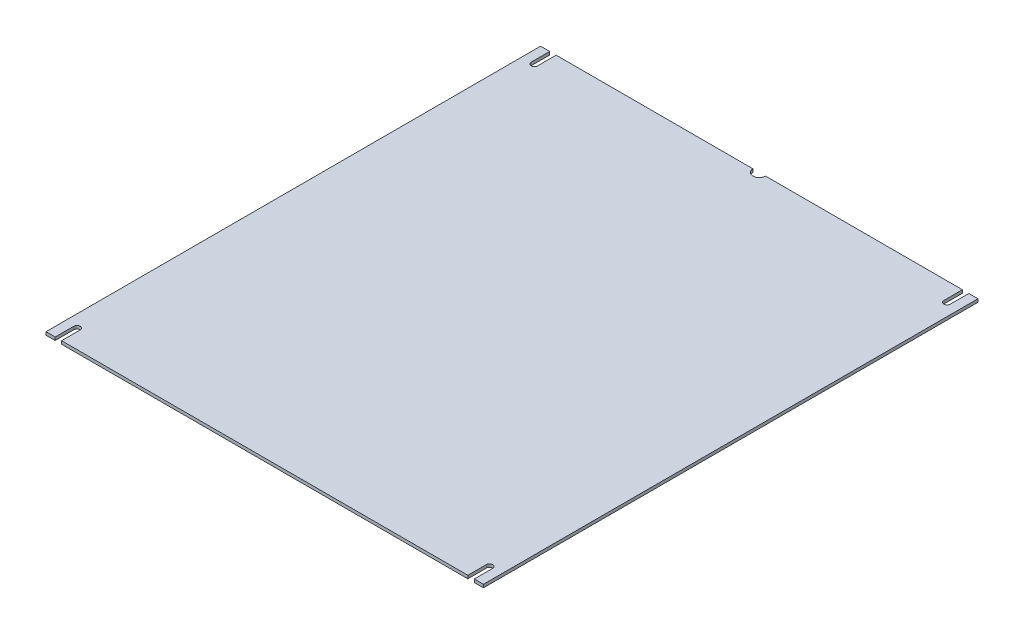
SolidWorks part; units mm, degrees
ref_plane "Front Plane" through (0, 0, 0) normal (0, 0, 1) x (1, 0, 0)
ref_plane "Top Plane" through (0, 0, 0) normal (0, 1, 0) x (1, 0, 0)
ref_plane "Right Plane" through (0, 0, 0) normal (1, 0, 0) x (0, 0, -1)
sketch "Sketch1" plane through (0, 0, 0) normal (0, 1, 0) x (1, 0, 0)
  line L1 (0, 0) -> (449.326, 0)
  line L2 (0, 0) -> (0, 508)
  line L3 (0, 508) -> (449.326, 508)
  line L4 (449.326, 0) -> (449.326, 508)
  dimension "D1" = 508
  dimension "D2" = 449.326
base flange "Base-Flange1" sketch "Sketch1" thickness 3.175 reverse thickness direction no parameters "D1"=0.7366
sketch "Sketch6" plane through (0, 0, 0) normal (0, 1, 0) x (1, 0, 0)
  line L0 (0, 508) -> (0, 0) construction
  line L1 (0, 0) -> (449.326, 0) construction
  line L2 (449.326, 0) -> (449.326, 508) construction
  line L3 (449.326, 508) -> (0, 508) construction
  line L4 (9.398, 19.05) -> (9.398, 0)
  line L5 (16.002, 19.05) -> (16.002, 0)
  line L6 (16.002, 0) -> (9.398, 0)
  line L7 (433.324, 19.05) -> (433.324, 0)
  line L8 (433.324, 0) -> (439.928, 0)
  line L9 (439.928, 0) -> (439.928, 19.05)
  line L10 (9.398, 488.95) -> (9.398, 508)
  line L11 (9.398, 508) -> (16.002, 508)
  line L12 (16.002, 508) -> (16.002, 488.95)
  line L13 (433.324, 488.95) -> (433.324, 508)
  line L14 (433.324, 508) -> (439.928, 508)
  line L15 (439.928, 508) -> (439.928, 488.95)
  line L16 (218.186, 508) -> (231.14, 508)
  arc A0 (16.002, 19.05) -> (9.398, 19.05) centre (12.7, 19.05) ccw
  arc A1 (9.398, 488.95) -> (16.002, 488.95) centre (12.7, 488.95) ccw
  arc A2 (433.324, 488.95) -> (439.928, 488.95) centre (436.626, 488.95) ccw
  arc A3 (439.928, 19.05) -> (433.324, 19.05) centre (436.626, 19.05) ccw
  arc A4 (218.186, 508) -> (231.14, 508) centre (224.663, 508) ccw
  dimension "D1" = 6.604
  dimension "D10" = 12.954
  dimension "D2" = 12.7
  dimension "D3" = 19.05
  dimension "D4" = 19.05
  dimension "D5" = 12.7
  dimension "D6" = 12.7
  dimension "D7" = 19.05
  dimension "D8" = 19.05
  dimension "D9" = 12.7
extrude "Cut-Extrude1" cut sketch "Sketch6" against normal through all normal cut yes
sketch "Bend-Lines1" plane through (0, 0, 0) normal (0, 1, 0) x (1, 0, 0)
sketch "Bounding-Box1" plane through (0, 0, 0) normal (0, 1, 0) x (1, 0, 0)
sheet metal parameters "Sheet-Metal(1)" thickness 3.175 parameters "D1"=0.7366
flat pattern "Flat-Pattern(1)" [suppressed]
sketch "Bend-Lines2" plane through (0, 0, 0) normal (0, 1, 0) x (1, 0, 0)
sketch "Bounding-Box2" [suppressed] plane through (0, 0, 0) normal (0, 1, 0) x (1, 0, 0)
sheet metal parameters "Sheet-Metal(2)" thickness 3.175 parameters "D1"=0.7366
flat pattern "Flat-Pattern(1)"
sketch "Bend-Lines2" plane through (0, 0, 0) normal (0, 1, 0) x (1, 0, 0)
sketch "Bounding-Box2" [suppressed] plane through (0, 0, 0) normal (0, 1, 0) x (1, 0, 0)
